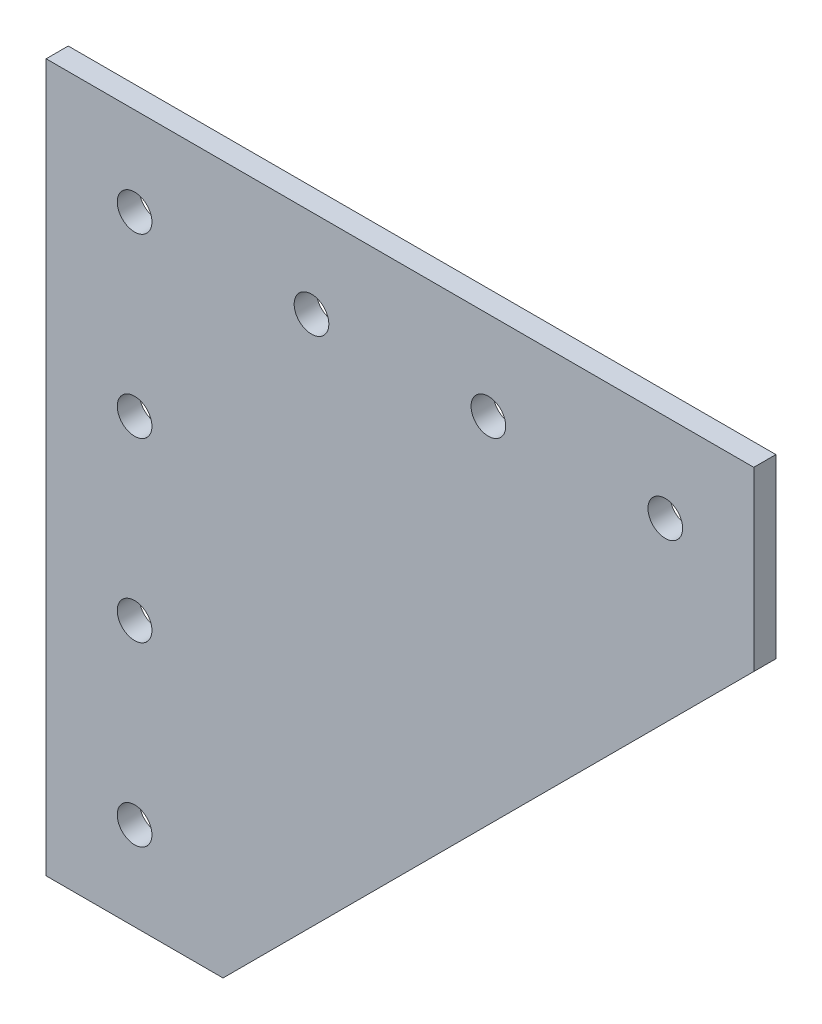
SolidWorks part; units mm, degrees
ref_plane "Front Plane" through (0, 0, 0) normal (0, 0, 1) x (1, 0, 0)
ref_plane "Top Plane" through (0, 0, 0) normal (0, 1, 0) x (1, 0, 0)
ref_plane "Right Plane" through (0, 0, 0) normal (1, 0, 0) x (0, 0, -1)
sketch "Sketch1" plane through (0, 0, 0) normal (0, 0, 1) x (1, 0, 0)
  line L0 (0, 0) -> (0, 101.6)
  line L1 (0, 101.6) -> (101.6, 101.6)
  line L2 (101.6, 101.6) -> (101.6, 76.2)
  line L5 (25.4, 0) -> (0, 0)
  line L6 (25.4, 0) -> (101.6, 76.2)
  dimension "D1" = 25.4
  dimension "D2" = 25.4
  dimension "D3" = 101.6
  dimension "D4" = 101.6
extrude "Boss-Extrude1" add sketch "Sketch1" along normal blind 3.175
sketch "Sketch2" plane through (0, 0, 3.175) normal (0, 0, 1) x (1, 0, 0)
  line L0 (101.6, 101.6) -> (0, 101.6) construction
  line L1 (0, 101.6) -> (0, 0) construction
  circle A0 centre (12.7, 88.9) radius 2.4892
  circle A5 centre (38.1, 88.9) radius 2.4892
  circle A6 centre (63.5, 88.9) radius 2.4892
  circle A8 centre (88.9, 88.9) radius 2.4892
  circle A9 centre (12.7, 63.5) radius 2.4892
  circle A10 centre (12.7, 38.1) radius 2.4892
  circle A11 centre (12.7, 12.7) radius 2.4892
  point P16 (0, 0)
  dimension "D1" = 12.7
  dimension "D2" = 25.4
  dimension "D3" = 25.4
  dimension "D4" = 25.4
  dimension "D5" = 12.7
  dimension "D6" = 4.9784
  dimension "D7" = 25.4
  dimension "D8" = 25.4
  dimension "D9" = 25.4
extrude "Cut-Extrude1" cut sketch "Sketch2" against normal through all
